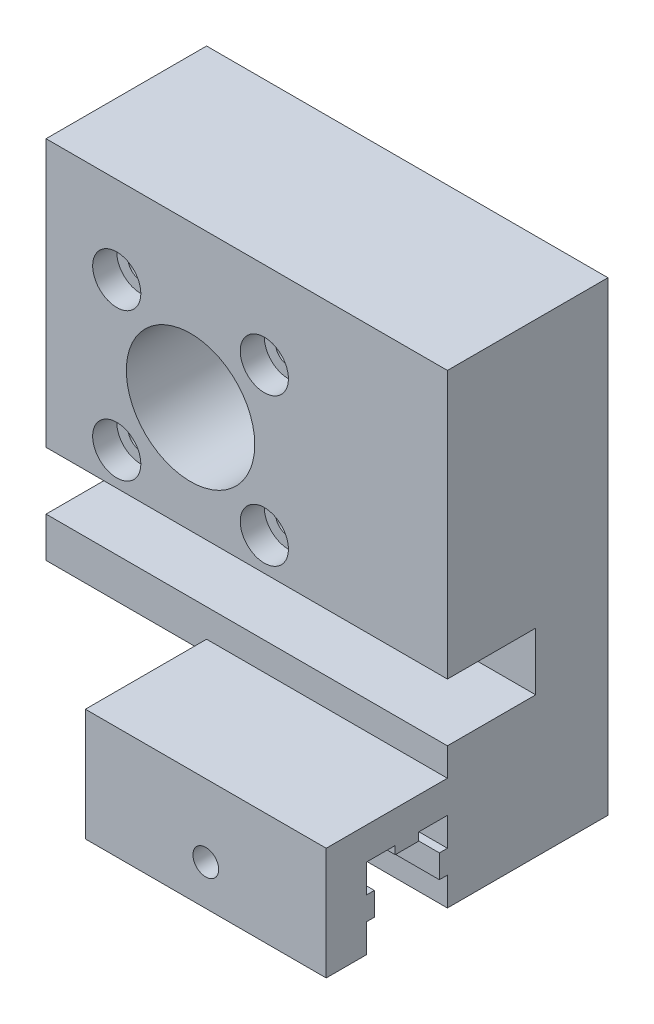
SolidWorks part; units mm, degrees
ref_plane "Front Plane" through (0, 0, 0) normal (0, 0, 1) x (1, 0, 0)
ref_plane "Top Plane" through (0, 0, 0) normal (0, 1, 0) x (1, 0, 0)
ref_plane "Right Plane" through (0, 0, 0) normal (1, 0, 0) x (0, 0, -1)
sketch "Esquisse1" plane through (0, 0, 0) normal (0, 0, 1) x (1, 0, 0)
  line L0 (25, 22.5) -> (25, -22.5)
  line L1 (-25, 22.5) -> (25, 22.5)
  line L2 (-25, 22.5) -> (-25, -22.5)
  line L3 (-25, -22.5) -> (25, -22.5)
  point P4 (-25, 0)
  point P6 (0, -22.5)
  dimension "D3" = 45
  dimension "D4" = 50
extrude "Main Extrusion" add sketch "Esquisse1" along normal blind 20
sketch "Esquisse5" plane through (0, 0, 20) normal (0, 0, 1) x (1, 0, 0)
  line L1 (-25, -22.5) -> (25, -22.5) construction
  line L3 (-25, 22.5) -> (-25, -22.5) construction
  circle A0 centre (-7, 2.5) radius 8
  dimension "D1" = 16
  dimension "D2" = 25
  dimension "D3" = 18
extrude "Gear Linear Holes" cut sketch "Esquisse5" against normal through all
sketch "Esquisse8" plane through (0, 0, 0) normal (1, 0, 0) x (0, 0, -1)
  line L0 (-20, -25.5) -> (-20, -29.05)
  line L1 (-20, -25.5) -> (-23.6, -25.5)
  line L2 (-23.6, -25.5) -> (-23.6, -26.5)
  line L3 (-23.6, -26.5) -> (-26.5, -26.5)
  line L4 (-26.5, -26.5) -> (-26.5, -25.5)
  line L5 (-35.1, -21.5) -> (0, -21.5)
  line L6 (-20, -35.5) -> (0, -35.5)
  line L7 (0, -35.5) -> (0, -21.5)
  line L8 (0, -22.5) -> (0, 22.5) construction
  line L9 (-26.5, -25.5) -> (-30.1, -25.5)
  line L10 (-20, -22.5) -> (0, -22.5) construction
  line L12 (0, 22.5) -> (0, -22.5) construction
  line L13 (-30.1, -25.5) -> (-30.1, -29.05)
  line L14 (-30.1, -35.5) -> (-35.1, -35.5)
  line L15 (-35.1, -35.5) -> (-35.1, -21.5)
  line L16 (-20, -29.05) -> (-21, -29.05)
  line L17 (-21, -29.05) -> (-21, -31.95)
  line L18 (-21, -31.95) -> (-20, -31.95)
  line L19 (-20, -31.95) -> (-20, -35.5)
  line L21 (-30.1, -29.05) -> (-29.1, -29.05)
  line L22 (-29.1, -29.05) -> (-29.1, -31.95)
  line L23 (-29.1, -31.95) -> (-30.1, -31.95)
  line L24 (-30.1, -31.95) -> (-30.1, -35.5)
  line L25 (-20, 22.5) -> (-20, -22.5) construction
  dimension "D1" = 2.9
  dimension "D2" = 10.1
  dimension "D3" = 1
  dimension "D4" = 3
  dimension "D5" = 10
  dimension "D6" = 5
  dimension "D7" = 4
extrude "Fixing Extrusion" add sketch "Esquisse8" along normal mid plane 50
sketch "Esquisse12" plane through (0, 0, 0) normal (0, 0, 1) x (1, 0, 0)
  circle A0 centre (-7, 2.5) radius 16
  dimension "D1" = 32
sketch "Esquisse13" plane through (0, 0, 20) normal (0, 0, 1) x (1, 0, 0)
  line L0 (-25, 22.5) -> (-25, -21.5) construction
  line L1 (-25, -18) -> (25, -18)
  line L2 (-25, -18) -> (-25, -10.8)
  line L3 (-25, -10.8) -> (25, -10.8)
  line L4 (25, -18) -> (25, -10.8)
  line L5 (25, -21.5) -> (25, 22.5) construction
  line L7 (-25, -21.5) -> (25, -21.5) construction
  dimension "D1" = 3.5
  dimension "D2" = 7.2
extrude "RollingBallHorizontalHole" cut sketch "Esquisse13" against normal blind 11
sketch "Esquisse14" plane through (-25, 0, 0) normal (-1, 0, 0) x (0, 0, 1)
  line L0 (0, -23) -> (20, -23)
  line L1 (0, -35.5) -> (35.1, -35.5)
  line L2 (0, -35.5) -> (0, -23)
  line L3 (20, -23) -> (20, -18)
  line L4 (35.1, -35.5) -> (35.1, -18)
  line L5 (20, -18) -> (35.1, -18)
  line L6 (20, -18) -> (20, -21.5) construction
  dimension "D1" = 12.5
extrude "FrontHole" cut sketch "Esquisse14" against normal blind 20
sketch "Esquisse15" plane through (0, 0, 35.1) normal (0, 0, 1) x (1, 0, 0)
  line L1 (25, -21.5) -> (25, -35.5) construction
  line L4 (-5, -31.95) -> (-5, -29.05) construction
  circle A1 centre (10, -30.5) radius 1.6
  point P5 (-5, -30.5)
  dimension "D1" = 3.2
  dimension "D2" = 15
extrude "BottomFixingHole" cut sketch "Esquisse15" against normal through all
extrude "ReductorMainHole" cut sketch "Esquisse12" along normal blind 5
sketch "Esquisse16" plane through (0, 0, 5) normal (0, 0, -1) x (-1, 0, 0)
  line L0 (2.6411, 11.5) -> (11.3589, 11.5)
  line L1 (2.6411, -6.5) -> (11.3589, -6.5)
  arc A0 (2.6411, 11.5) -> (2.6411, -6.5) centre (7, 2.5) ccw
  arc A2 (11.3589, 11.5) -> (11.3589, -6.5) centre (7, 2.5) cw
  circle A3 centre (7, 2.5) radius 16 construction
  dimension "D1" = 10
  dimension "D2" = 18
extrude "ReductorFrontFixingHole" cut sketch "Esquisse16" against normal blind 3
sketch "Esquisse17" plane through (0, 0, 5) normal (0, 0, -1) x (-1, 0, 0)
  line L0 (7, 2.5) -> (-2.1924, 11.6924) construction
  line L1 (11, 0) -> (-11, 0) construction
  line L2 (-2.1924, -6.6924) -> (16.1924, 11.6924) construction
  line L3 (7, 2.5) -> (16.1924, -6.6924) construction
  circle A0 centre (-2.1924, 11.6924) radius 1.6
  circle A1 centre (16.1924, 11.6924) radius 1.6
  circle A2 centre (-2.1924, -6.6924) radius 1.6
  circle A3 centre (16.1924, -6.6924) radius 1.6
  dimension "D1" = 3.2
  dimension "D2" = 45
  dimension "D3" = 13
  dimension "D4" = 13
  dimension "D5" = 13
extrude "MotorFixingHole" cut sketch "Esquisse17" against normal through all
sketch "Esquisse19" plane through (0, 0, 20) normal (0, 0, 1) x (1, 0, 0)
  circle A0 centre (-16.1924, 11.6924) radius 3
  circle A1 centre (2.1924, 11.6924) radius 3
  circle A2 centre (-16.1924, -6.6924) radius 3
  circle A3 centre (2.1924, -6.6924) radius 3
  dimension "D1" = 6
extrude "Enlèv. mat.-Extru.5" cut sketch "Esquisse19" against normal blind 3
